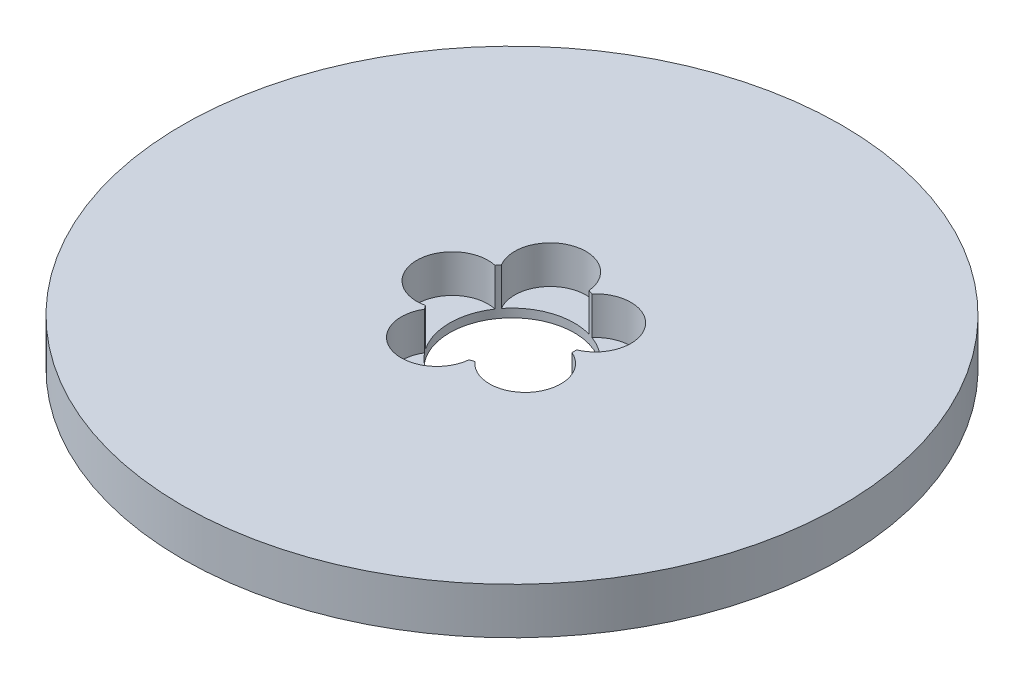
SolidWorks part; units mm, degrees
ref_plane "Front Plane" through (0, 0, 0) normal (0, 0, 1) x (1, 0, 0)
ref_plane "Top Plane" through (0, 0, 0) normal (0, 1, 0) x (1, 0, 0)
ref_plane "Right Plane" through (0, 0, 0) normal (1, 0, 0) x (0, 0, -1)
sketch "Sketch1" plane through (0, 0, 0) normal (0, 1, 0) x (1, 0, 0)
  circle A0 centre (0, 0) radius 92.5
  dimension "FLANGE_OD" = 185
extrude "Boss-Extrude1" add sketch "Sketch1" along normal blind 13
sketch "Sketch2" plane through (0, 0, 0) normal (0, 1, 0) x (1, 0, 0)
  circle A0 centre (0, 0) radius 17.5
  dimension "BORE_D" = 35
extrude "Cut-Extrude1" cut sketch "Sketch2" along normal through all
sketch "Sketch3" plane through (0, 13, 0) normal (0, 1, 0) x (1, 0, 0)
  circle A0 centre (0, 0) radius 16.7353 construction
  circle A1 centre (-16.7353, 0) radius 10
  dimension "BOLT_D" = 20
  dimension "BOLT_PCD" = 33.4705
extrude "Cut-Extrude2" cut sketch "Sketch3" against normal blind 10.6183
pattern_circular "CirPattern1" count 5 over 360 about axis through (0, 0, 0) along (0, 1, 0) of "Cut-Extrude2"
